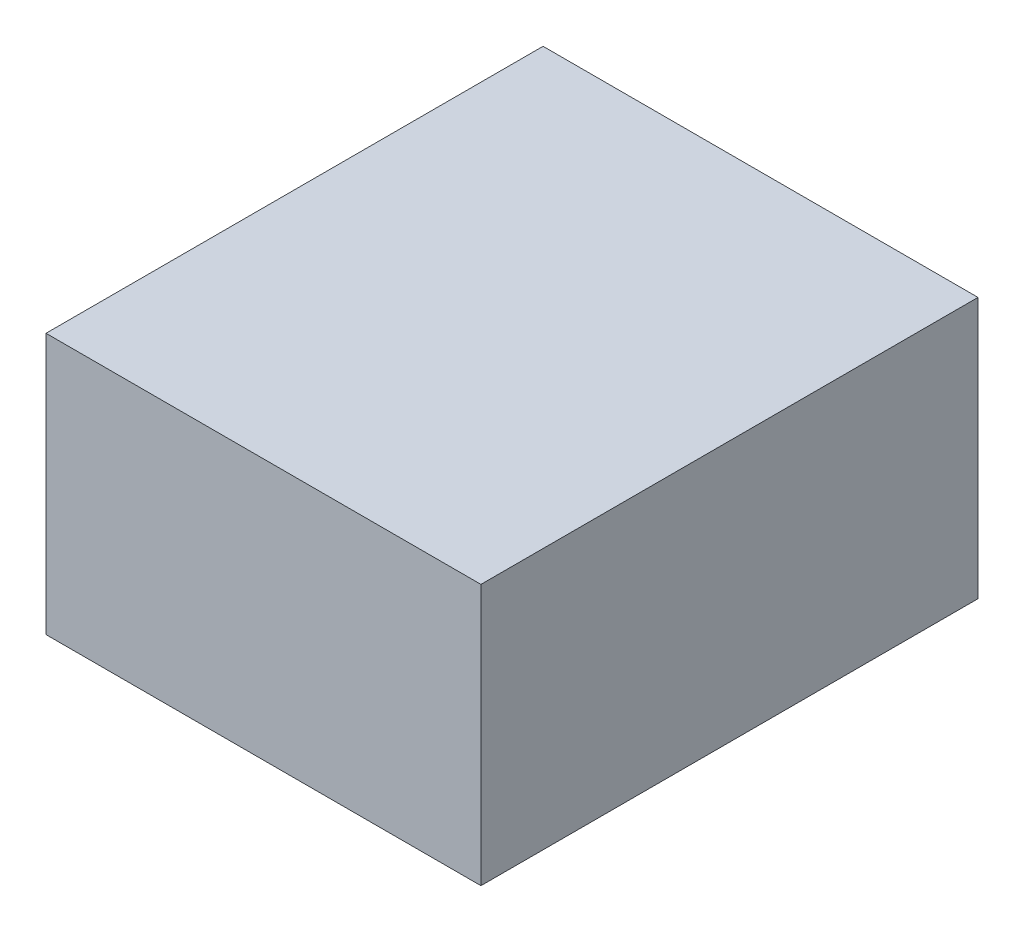
SolidWorks part; units mm, degrees
ref_plane "Front Plane" through (0, 0, 0) normal (0, 0, 1) x (1, 0, 0)
ref_plane "Top Plane" through (0, 0, 0) normal (0, 1, 0) x (1, 0, 0)
ref_plane "Right Plane" through (0, 0, 0) normal (1, 0, 0) x (0, 0, -1)
sketch "Sketch1" plane through (0, 0, 0) normal (0, 0, 1) x (1, 0, 0)
  line L1 (-4.6054, 5.2352) -> (4.2846, 5.2352)
  line L2 (-4.6054, 5.2352) -> (-4.6054, -0.0988)
  line L3 (-4.6054, -0.0988) -> (4.2846, -0.0988)
  line L4 (4.2846, 5.2352) -> (4.2846, -0.0988)
  dimension "D1" = 8.89
  dimension "D2" = 5.334
extrude "Boss-Extrude1" add sketch "Sketch1" along normal blind 10.16
